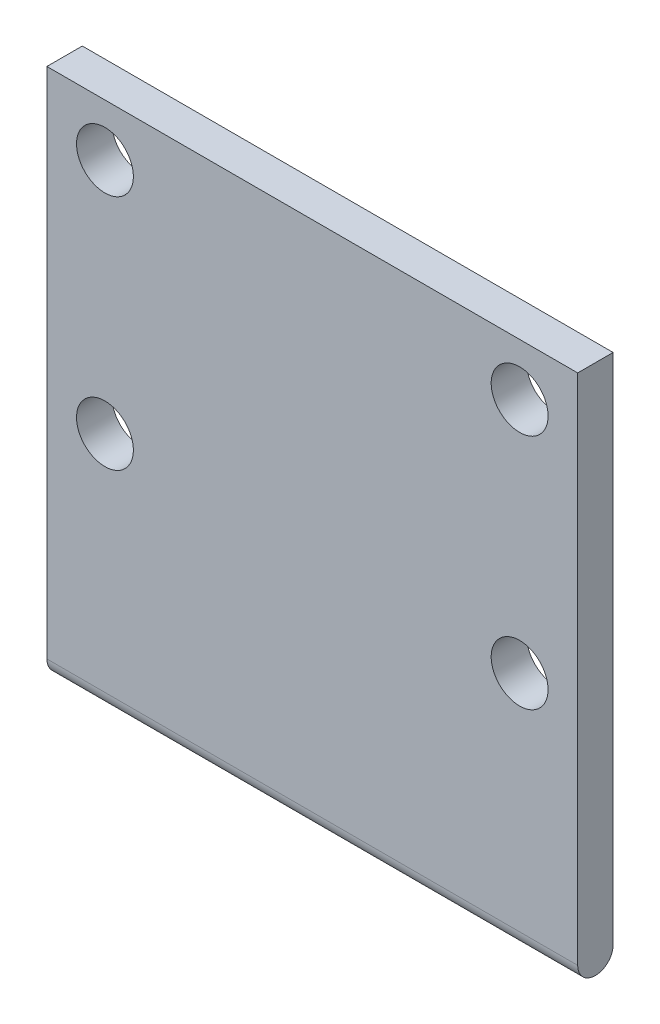
SolidWorks part; units mm, degrees
ref_plane "Front Plane" through (0, 0, 0) normal (0, 0, 1) x (1, 0, 0)
ref_plane "Top Plane" through (0, 0, 0) normal (0, 1, 0) x (1, 0, 0)
ref_plane "Right Plane" through (0, 0, 0) normal (1, 0, 0) x (0, 0, -1)
sketch "Sketch1" plane through (0, 0, 0) normal (0, 1, 0) x (1, 0, 0)
  line L1 (-22.4, -1.495) -> (22.4, -1.495)
  line L2 (-22.4, -1.495) -> (-22.4, 1.495)
  line L3 (-22.4, 1.495) -> (22.4, 1.495)
  line L4 (22.4, -1.495) -> (22.4, 1.495)
  line L5 (-22.4, -1.495) -> (22.4, 1.495) construction
  line L6 (-22.4, 1.495) -> (22.4, -1.495) construction
  point P0 (0, 0)
  dimension "D1" = 44.8
  dimension "D2" = 2.99
extrude "Boss-Extrude1" add sketch "Sketch1" along normal blind 44.8
sketch "Sketch2" plane through (0, 0, 1.495) normal (0, 0, 1) x (1, 0, 0)
  line L0 (-22.4, 0) -> (22.4, 0) construction
  line L1 (-7.5, 8.2) -> (7.5, 8.2)
  point P0 (0, 8.025)
  point P1 (0, 8.2)
  dimension "D1" = 8.2
  dimension "D2" = 15
fillet "Fillet1" 2 edges at (0, 0, 1.495) (0, 0, -1.495) type full round first side face at (0, 22.4, 1.495) second side face at (0, 22.4, -1.495) middle face at (0, 0, 0) tangent propagation no
sketch "Sketch3" plane through (0, 0, 1.495) normal (0, 0, 1) x (1, 0, 0)
  line L0 (0, 0) -> (0, 16) construction
  line L1 (-22.4, 16) -> (22.4, 16) construction
  line L2 (22.4, 44.8) -> (22.4, 1.495) construction
  line L4 (17.5, 20.4) -> (-17.5, 20.4)
  line L5 (17.5, 20.4) -> (17.5, 40.4)
  line L6 (17.5, 40.4) -> (-17.5, 40.4)
  line L7 (-17.5, 20.4) -> (-17.5, 40.4)
  line L8 (17.5, 20.4) -> (-17.5, 40.4) construction
  line L9 (17.5, 40.4) -> (-17.5, 20.4) construction
  point P3 (0, 30.4)
  point P8 (0, 16)
  dimension "D1" = 16
  dimension "D2" = 4.4
  dimension "D3" = 35
  dimension "D4" = 20
hole_wizard "M4 Clearance Hole1" positions "Sketch4" profile "Sketch5" hole size "M4" standard "ANSI Metric" end condition up to next
sketch "Sketch4" plane through (0, 0, 1.495) normal (0, 0, 1) x (1, 0, 0)
  point P0 (-17.5, 40.4)
  point P3 (-17.5, 20.4)
  point P6 (17.5, 20.4)
  point P9 (17.5, 40.4)
sketch "Sketch5" plane through (-17.5, 40.4, 1.495) normal (1, 0, 0) x (0, -1, 0)
  line L0 (0, 0) -> (0, 2.99)
  line L1 (0, 2.99) -> (2.4, 2.99)
  line L2 (2.4, 2.99) -> (2.4, 0)
  line L5 (2.4, 0) -> (0, 0)
  line L11 (0, -6.35) -> (0, 107.95) construction
  dimension "Thru Hole Dia." = 4.8
  dimension "Thru Hole Depth" = 2.99
sketch "Sketch8" plane through (0, 0, 1.495) normal (0, 0, 1) x (1, 0, 0)
  circle A0 centre (-7.5, 8.2) radius 1.4819
  circle A1 centre (7.5, 8.2) radius 1.2496
extrude "Boss-Extrude2" add sketch "Sketch8" against normal blind 6.99
sketch "Sketch9" plane through (0, 0, -5.495) normal (0, 0, -1) x (-1, 0, 0)
  line L0 (7.5, 9.6819) -> (7.5, 6.7181)
  arc A0 (7.5, 6.7181) -> (7.5, 9.6819) centre (7.5, 8.2) ccw
revolve "Revolve1" add sketch "Sketch9" angle 180 about L0
sketch "Sketch10" plane through (0, 0, -5.495) normal (0, 0, -1) x (-1, 0, 0)
  line L0 (-7.5, 9.4496) -> (-7.5, 6.9504)
  arc A0 (-7.5, 6.9504) -> (-7.5, 9.4496) centre (-7.5, 8.2) ccw
revolve "Revolve2" add sketch "Sketch10" angle 180 about L0
